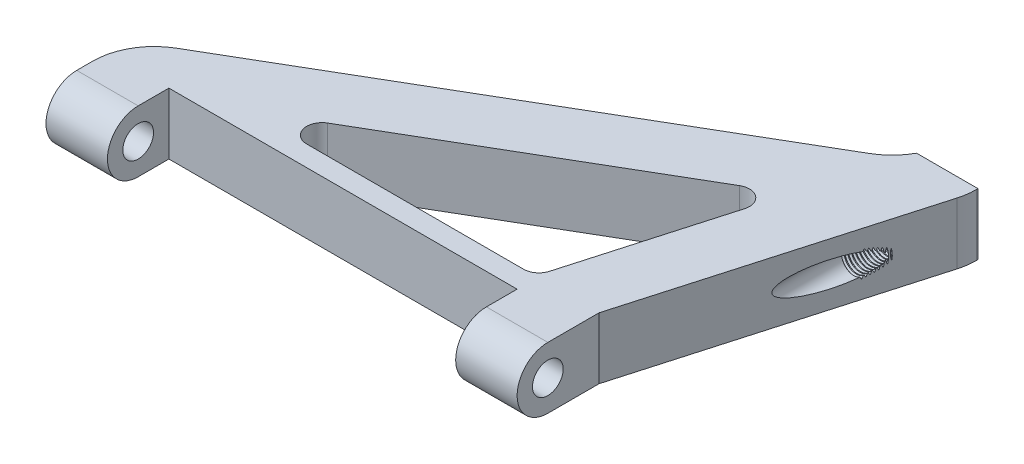
SolidWorks part; units mm, degrees
other "Markup1"
sketch "Sketch9" plane through (-9.525, 19.05, 0) normal (-0.761, 0.4779, -0.4388) x (-0.0596, 0.622, 0.7808)
material "6061-T6 (SS)"
ref_plane "Front Plane" through (0, 0, 0) normal (0, 0, 1) x (1, 0, 0)
ref_plane "Top Plane" through (0, 0, 0) normal (0, 1, 0) x (1, 0, 0)
ref_plane "Right Plane" through (0, 0, 0) normal (1, 0, 0) x (0, 0, -1)
sketch "Sketch1" plane through (0, 0, 0) normal (0, 1, 0) x (1, 0, 0)
  line L0 (0, 0) -> (0, -117.475) construction
  line L1 (0, 0) -> (152.4, 0) construction
  line L2 (152.4, 0) -> (152.4, -38.1) construction
  line L3 (142.875, 0) -> (161.925, 0)
  line L4 (161.925, 0) -> (161.925, -3.175)
  line L5 (0, -117.475) -> (0, -107.95)
  line L7 (9.525, -117.475) -> (-9.525, -117.475)
  line L8 (142.875, 0) -> (142.875, -3.175)
  line L12 (9.525, -98.425) -> (9.525, -117.475)
  line L13 (0, 0) -> (127, -117.475) construction
  line L14 (127, -117.475) -> (-9.525, -117.475) construction
  line L15 (136.525, -117.475) -> (117.475, -117.475)
  line L16 (117.475, -117.475) -> (117.475, -98.425)
  line L17 (136.525, -117.475) -> (136.525, -92.075)
  line L20 (136.525, -92.075) -> (161.925, -3.175)
  line L21 (9.525, -98.425) -> (117.475, -98.425)
  line L23 (9.525, -98.425) -> (9.525, -35.1596) construction
  line L24 (117.475, -98.425) -> (117.475, -50.2412) construction
  line L25 (-9.525, -92.075) -> (136.525, -92.075) construction
  line L26 (-9.525, -75.448) -> (75.6321, -5.5325) construction
  line L27 (131.144, -41.5655) -> (117.6996, -88.6209)
  line L28 (124.165, -36.1434) -> (43.4987, -83.1988)
  line L29 (45.8984, -92.075) -> (113.1203, -92.075)
  line L31 (-9.525, -92.075) -> (142.875, -3.175)
  line L32 (-9.525, -117.475) -> (-9.525, -92.075)
  line L33 (142.875, -3.175) -> (161.925, -3.175) construction
  arc A7 (45.8984, -92.075) -> (43.4987, -83.1988) centre (45.8984, -87.3125) cw
  arc A8 (113.1203, -92.075) -> (117.6996, -88.6209) centre (113.1203, -87.3125) ccw
  arc A9 (124.165, -36.1434) -> (131.144, -41.5655) centre (126.5647, -40.2571) cw
  point P7 (152.4, 0)
  point P11 (63.5, -92.075)
  point P13 (0, -107.95)
  point P16 (0, -117.475)
  point P20 (127, -117.475)
  point P28 (116.7127, -92.075)
  point P31 (-9.525, -41.275)
  point P36 (152.4, -30.8241)
  point P45 (162.8454, -13.5799)
  point P48 (9.525, -92.075)
  dimension "D12" = 6.35
  dimension "D13" = 19.05
  dimension "D14" = 19.05
  dimension "D18" = 4.7625
  dimension "D15" = 4.7625
  dimension "D2" = 161.925
  dimension "D3" = 38.1
  dimension "D4" = 3.175
  dimension "D5" = 76.2
  dimension "D6" = 19.05
  dimension "D7" = 127
  dimension "D8" = 19.05
  dimension "D9" = 114.3
  dimension "D10" = 19.05
  dimension "D11" = 19.05
extrude "Boss-Extrude1" add sketch "Sketch1" along normal blind 19.05 contours L12 L21 L16 L15 L17 L20 L4 L3 L8 L7 region at (152.4, 0, 2.0784)
sketch "Sketch3" plane through (0, 0, 0) normal (0, 0, -1) x (-1, 0, 0)
  line L0 (-142.875, 19.05) -> (-161.925, 19.05) construction
  line L1 (-161.925, 19.05) -> (-161.925, 0) construction
  circle A0 centre (-152.4, 9.525) radius 3.9687
  dimension "D1" = 7.9375
  dimension "D3" = 9.525
  dimension "D2" = 9.525
extrude "Cut-Extrude1" cut sketch "Sketch3" against normal up to next
fillet "Fillet1" 2 edges at (0, 19.05, 117.475) (0, 0, 117.475) type full round first side face at (93.1333, 19.05, 71.4375) second side face at (93.1333, 0, 71.4375) middle face at (0, 9.525, 117.475)
sketch "Sketch6" plane through (136.525, 0, 0) normal (1, 0, 0) x (0, 0, -1)
  line L0 (-117.475, 0) -> (-92.075, 0) construction
  circle A0 centre (-107.95, 9.525) radius 4.7625
  dimension "D1" = 9.525
  dimension "D2" = 9.525
  dimension "D3" = 9.525
extrude "Cut-Extrude3" cut sketch "Sketch6" against normal through all
fillet "Fillet2" 2 edges at (127, 19.05, 117.475) (127, 0, 117.475) type full round first side face at (93.1333, 19.05, 69.85) second side face at (93.1333, 0, 69.85) middle face at (127, 9.525, 117.475)
fillet "Fillet3" radius 19.05 2 edges at (161.925, 9.525, 3.175) (142.875, 9.525, 3.175)
fillet "Fillet6" radius 19.05 1 edges at (-9.525, 9.525, 92.075)
sketch "Sketch8" [suppressed] plane through (0, 19.05, 0) normal (0, 1, 0) x (1, 0, 0)
  line L4 (124.165, -36.1434) -> (43.4987, -83.1988) construction
  line L10 (160.5971, -158.3087) -> (103.1838, -57.8355)
  line L11 (130.8738, -89.8648) -> (115.3014, -62.613)
  line L12 (160.1788, -156.7334) -> (160.1788, 27.2514)
  line L13 (126.0432, -94.615) -> (128.1172, -94.615)
  line L14 (136.525, -92.075) -> (161.192, -5.7404) construction
  line L15 (81.7133, -27.9414) -> (112.9323, -82.5745) construction
  line L16 (156.3688, -22.6219) -> (156.3688, 0) construction
  line L17 (9.525, -98.425) -> (117.475, -98.425) construction
  line L18 (108.2246, -66.6568) -> (123.2866, -93.0152)
  line L19 (109.406, -62.3249) -> (110.9695, -61.4315)
  line L20 (107.5158, -59.0169) -> (147.6154, -36.1028)
  line L21 (149.093, -34.2184) -> (166.4066, 26.3792)
  line L34 (144.6213, -12.095) -> (144.6213, -17.9761)
  line L35 (122.2453, -32.8524) -> (41.579, -79.9078)
  line L36 (143.046, -20.7186) -> (113.4191, -38.001)
  line L37 (148.4313, 0) -> (148.4313, -50.4031) construction
  line L38 (98.8839, -33.2473) -> (3.8265, -88.6975)
  line L39 (109.0769, -36.8583) -> (106.5172, -32.4703)
  line L40 (105.7859, -38.778) -> (103.2262, -34.39)
  line L41 (104.6431, -43.1203) -> (17.108, -94.1825)
  line L45 (137.6708, -10.6216) -> (1.846, -89.8528)
  line L46 (-5.715, -103.0168) -> (-5.715, -104.14)
  line L47 (-5.715, -104.14) -> (5.715, -104.14)
  line L48 (5.715, -104.14) -> (5.715, -94.615)
  line L49 (5.715, -94.615) -> (121.285, -94.615)
  line L50 (121.285, -94.615) -> (121.285, -104.14)
  line L51 (121.285, -104.14) -> (132.715, -104.14)
  line L52 (132.715, -104.14) -> (132.715, -91.5414)
  line L53 (132.715, -91.5414) -> (157.5286, -4.6937)
  line L55 (157.7528, -3.81) -> (145.0012, -3.81)
  line L57 (139.8465, -9.3525) -> (107.6599, -28.128)
  line L61 (5.4262, -94.615) -> (15.5082, -94.615)
  line L65 (132.715, -91.5414) -> (157.5286, -4.6937)
  arc A6 (123.2866, -93.0152) -> (126.0432, -94.615) centre (126.0432, -91.44) ccw
  arc A7 (130.8738, -89.8648) -> (128.1172, -94.615) centre (128.1172, -91.44) cw
  arc A8 (110.9695, -61.4315) -> (115.3014, -62.613) centre (112.5447, -64.1882) cw
  arc A9 (109.406, -62.3249) -> (108.2246, -66.6568) centre (110.9813, -65.0816) ccw
  arc A10 (107.5158, -59.0169) -> (103.1838, -57.8355) centre (105.9405, -56.2603) cw
  arc A11 (147.6154, -36.1028) -> (149.093, -34.2184) centre (146.0402, -33.3462) ccw
  arc A12 (160.5971, -158.3087) -> (160.1788, -156.7334) centre (163.3538, -156.7334) cw
  arc A13 (160.1788, 27.2514) -> (166.4066, 26.3792) centre (163.3538, 27.2514) cw
  arc A14 (144.6213, -12.095) -> (139.8465, -9.3525) centre (141.4462, -12.095) ccw
  arc A15 (17.108, -94.1825) -> (15.5082, -94.615) centre (15.5082, -91.44) cw
  arc A16 (3.8265, -88.6975) -> (5.4262, -94.615) centre (5.4262, -91.44) ccw
  arc A17 (105.7859, -38.778) -> (104.6431, -43.1203) centre (103.0434, -40.3778) cw
  arc A18 (103.2262, -34.39) -> (98.8839, -33.2473) centre (100.4837, -35.9898) ccw
  arc A19 (106.5172, -32.4703) -> (107.6599, -28.128) centre (109.2597, -30.8705) cw
  arc A20 (109.0769, -36.8583) -> (113.4191, -38.001) centre (111.8194, -35.2585) ccw
  arc A21 (144.6213, -17.9761) -> (143.046, -20.7186) centre (141.4462, -17.9761) cw
  arc A26 (1.846, -89.8528) -> (-5.715, -103.0168) centre (9.525, -103.0168) ccw
  arc A28 (157.5286, -4.6937) -> (157.7528, -3.81) centre (142.875, -0.507) ccw
  arc A29 (137.6708, -10.6216) -> (145.0012, -3.81) centre (126.1523, 9.1243) ccw
  dimension "D4" = 3.81
  dimension "D5" = 3.175
  dimension "D3" = 3.81
  dimension "D6" = 3.175
  dimension "D7" = 3.81
  dimension "D10" = 3.175
  dimension "D2" = 3.81
  dimension "D8" = 3.81
  dimension "D9" = 3.81
  dimension "D11" = 3.81
  dimension "D12" = 3.81
  dimension "D13" = 3.81
  dimension "D15" = 43.18
  dimension "D16" = 48.7737
extrude "Cut-Extrude4" [suppressed] cut sketch "Sketch8" against normal blind 12.7 contours A21 L34 A14 L57 A19 L39 A20 L36 | L40 A18 L38 A16 L61 A15 L41 A17 | A13 L12 A12 L10 A10 L20 A11 L21 | L19 A9 L18 A6 L13 A7 L11 A8
thread "Thread2" pitch 1.0583 method cut profile "Thread Profile2" start angle 0, offset 0, length 28.575, pitch 1.0583, diameter 7.9375
ref_plane "Plane2" through (156.3688, 9.525, 0) normal (0, -1, 0) x (1, 0, 0)
sketch "Thread Profile2" plane through (156.3688, 9.525, 0) normal (0, -1, 0) x (1, 0, 0)
  line L0 (0, 0) -> (0, 1.0583) construction
  line L1 (0, 0) -> (0.5728, 0.3307)
  line L2 (0.5728, 0.3307) -> (0.5728, 0.463)
  line L3 (0.5728, 0.463) -> (0, 0.7937)
  line L4 (0.5728, 0.3969) -> (0, 0.3969) construction
  line L11 (0, 0) -> (0, 0.7937)
  point P2 (0, 0)
  dimension "Pitch" = 1.0583
  dimension "Profile_Angle" = 60
  dimension "Profile_Land" = 0.1323
  dimension "Profile_Height" = 0.5728
sketch "Sketch10" plane through (0, 0, 0) normal (1, 0, 0) x (0, 0, -1)
  point P0 (-107.95, 9.525)
sketch3d "3DSketch2"
  line L0 (0, 9.525, 107.95) -> (167.6024, 9.525, 107.95) construction
move or copy body "Body-Move/Copy2" [suppressed] bodies to move or copy 105
move or copy body "Body-Move/Copy1" [suppressed] bodies to move or copy 105
